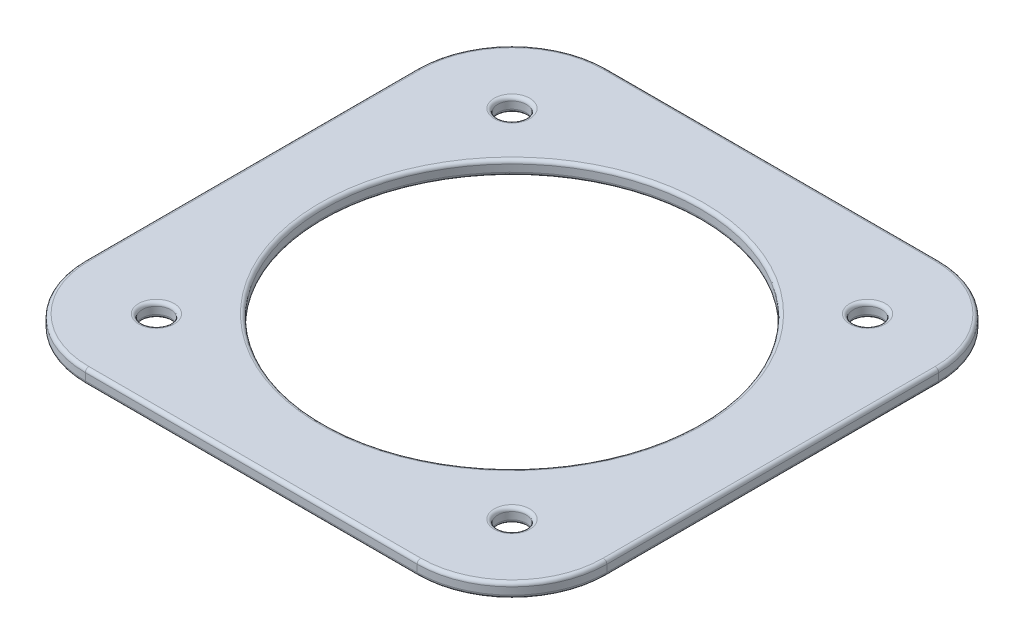
SolidWorks part; units mm, degrees
material "ABS"
ref_plane "Front Plane" through (0, 0, 0) normal (0, 0, 1) x (1, 0, 0)
ref_plane "Top Plane" through (0, 0, 0) normal (0, 1, 0) x (1, 0, 0)
ref_plane "Right Plane" through (0, 0, 0) normal (1, 0, 0) x (0, 0, -1)
sketch "Sketch1" plane through (0, 0, 0) normal (0, 1, 0) x (1, 0, 0)
  line L1 (-70, -110) -> (70, -110)
  line L2 (-110, -70) -> (-110, 70)
  line L3 (-70, 110) -> (70, 110)
  line L4 (110, -70) -> (110, 70)
  line L5 (-110, -110) -> (110, 110) construction
  line L6 (-110, 110) -> (110, -110) construction
  circle A1 centre (0, 0) radius 79.5
  arc A2 (-70, -110) -> (-110, -70) centre (-70, -70) cw
  circle A3 centre (0, 0) radius 87.5 construction
  arc A4 (70, -110) -> (110, -70) centre (70, -70) ccw
  arc A5 (70, 110) -> (110, 70) centre (70, 70) cw
  arc A6 (-110, 70) -> (-70, 110) centre (-70, 70) cw
  dimension "D1" = 220
  dimension "D2" = 8
  dimension "D3" = 40
extrude "Boss-Extrude1" add sketch "Sketch1" along normal blind 6
hole_wizard "CBORE for M10 SHCS" positions "Sketch2" profile "Sketch3" counterbore size "M10" standard "ANSI Metric" end condition through all
sketch "Sketch2" plane through (0, 21, 0) normal (0, 1, 0) x (1, 0, 0)
  line L1 (75, -75) -> (-75, -75) construction
  line L2 (75, -75) -> (75, 75) construction
  line L3 (75, 75) -> (-75, 75) construction
  line L4 (-75, -75) -> (-75, 75) construction
  line L5 (75, -75) -> (-75, 75) construction
  line L6 (75, 75) -> (-75, -75) construction
  line L7 (-250, 0) -> (0, 250) construction
  line L8 (-250, 0) -> (0, -250) construction
  line L9 (0, 250) -> (250, 0) construction
  line L10 (0, -250) -> (250, 0) construction
  line L11 (-250, 0) -> (250, 0) construction
  line L12 (0, 250) -> (0, -250) construction
  point P36 (0, 0)
  point P198 (-75, 75)
  point P201 (75, 75)
  point P204 (75, -75)
  point P207 (-75, -75)
  point P210 (0, 0)
  point P341 (0, 250)
  point P344 (-250, 0)
  point P347 (250, 0)
  point P350 (0, -250)
sketch "Sketch3" plane through (0, 21, 0) normal (1, 0, 0) x (0, 0, 1)
  line L0 (0, 0) -> (0, 21)
  line L1 (0, 21) -> (6, 21)
  line L2 (6, 21) -> (6, 10)
  line L3 (6, 10) -> (9, 10)
  line L4 (9, 10) -> (9, 0)
  line L5 (9, 0) -> (0, 0)
  line L6 (0, -6.35) -> (0, 107.95) construction
  dimension "Thru Hole Dia." = 12
  dimension "Thru Hole Depth" = 21
  dimension "C'Bore Dia." = 18
  dimension "C'Bore Depth" = 10
fillet "Fillet1" radius 1.5 26 edges at (0, 0, 79.5) (0, 0, 110) (98.2843, 0, 98.2843) (110, 0, 0) (98.2843, 0, -98.2843) (0, 0, -110) (-98.2843, 0, -98.2843) (-110, 0, 0) (-98.2843, 0, 98.2843) (0, 6, 79.5) (-110, 6, 0) (-98.2843, 6, -98.2843) (0, 6, -110) (98.2843, 6, -98.2843) (110, 6, 0) (98.2843, 6, 98.2843) (0, 6, 110) (-98.2843, 6, 98.2843) (-75, 0, 81) (75, 0, 81) (75, 0, -69) (-75, 0, -69) (-75, 6, 69) (75, 6, 69) (75, 6, -81) (-75, 6, -81)
